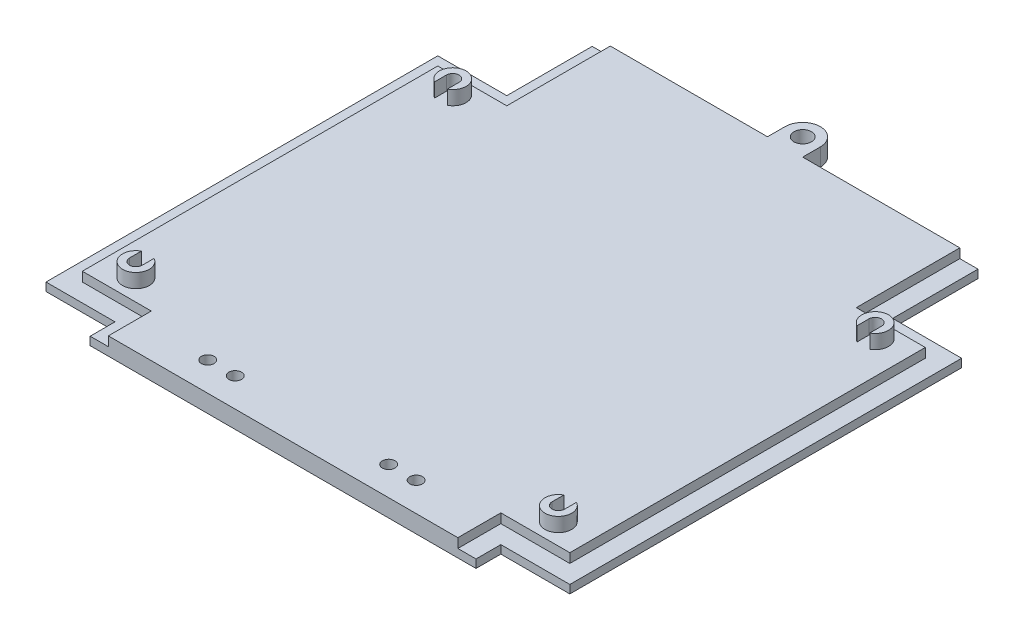
SolidWorks part; units mm, degrees
ref_plane "Front Plane" through (0, 0, 0) normal (0, 0, 1) x (1, 0, 0)
ref_plane "Top Plane" through (0, 0, 0) normal (0, 1, 0) x (1, 0, 0)
ref_plane "Right Plane" through (0, 0, 0) normal (1, 0, 0) x (0, 0, -1)
sketch "Sketch1" plane through (0, 0, 0) normal (0, 1, 0) x (1, 0, 0)
  line L0 (0, 150.2994) -> (0, 181.102)
  line L1 (0, 0) -> (139.192, 0)
  line L2 (0, 0) -> (0, 8.9586)
  line L3 (0, 181.102) -> (139.192, 181.102)
  line L4 (139.192, 0) -> (139.192, 8.9586)
  line L5 (0, 150.2994) -> (-24.892, 150.2994)
  line L7 (0, 8.9586) -> (-24.892, 8.9586)
  line L8 (-24.892, 150.2994) -> (-24.892, 8.9586)
  line L9 (139.192, 8.9586) -> (164.084, 8.9586)
  line L11 (139.192, 150.2994) -> (164.084, 150.2994)
  line L12 (164.084, 8.9586) -> (164.084, 150.2994)
  line L13 (139.192, 150.2994) -> (139.192, 181.102)
  dimension "D1" = 139.192
  dimension "D2" = 181.102
  dimension "D3" = 24.892
  dimension "D4" = 30.8026
  dimension "D5" = 8.9586
extrude "Boss-Extrude1" add sketch "Sketch1" along normal blind 6.35
sketch "Sketch2" plane through (0, 6.35, 0) normal (0, 1, 0) x (1, 0, 0)
  line L0 (69.596, 181.102) -> (69.596, 0) construction
  line L1 (139.192, 181.102) -> (0, 181.102) construction
  line L2 (0, 0) -> (139.192, 0) construction
  line L11 (132.642, 181.102) -> (132.642, 143.7494)
  line L12 (139.192, 181.102) -> (0, 181.102) construction
  line L13 (132.642, 143.7494) -> (157.534, 143.7494)
  line L14 (157.534, 143.7494) -> (157.534, 15.5086)
  line L15 (157.534, 15.5086) -> (132.642, 15.5086)
  line L16 (132.642, 15.5086) -> (132.642, 0)
  line L17 (132.642, 0) -> (139.192, 0)
  line L18 (139.192, 0) -> (139.192, 8.9586)
  line L19 (139.192, 8.9586) -> (164.084, 8.9586)
  line L20 (164.084, 8.9586) -> (164.084, 150.2994)
  line L21 (164.084, 150.2994) -> (139.192, 150.2994)
  line L22 (139.192, 150.2994) -> (139.192, 181.102)
  line L23 (139.192, 181.102) -> (132.642, 181.102)
  line L24 (0, 181.102) -> (6.55, 181.102)
  line L25 (0, 150.2994) -> (0, 181.102)
  line L26 (-24.892, 150.2994) -> (0, 150.2994)
  line L27 (-24.892, 8.9586) -> (-24.892, 150.2994)
  line L28 (0, 8.9586) -> (-24.892, 8.9586)
  line L29 (0, 0) -> (0, 8.9586)
  line L30 (6.55, 0) -> (0, 0)
  line L31 (6.55, 15.5086) -> (6.55, 0)
  line L32 (-18.342, 15.5086) -> (6.55, 15.5086)
  line L33 (-18.342, 143.7494) -> (-18.342, 15.5086)
  line L34 (6.55, 143.7494) -> (-18.342, 143.7494)
  line L35 (6.55, 181.102) -> (6.55, 143.7494)
  dimension "D1" = 6.55
  dimension "D2" = 6.55
  dimension "D3" = 6.55
  dimension "D4" = 6.55
  dimension "D5" = 6.55
extrude "Cut-Extrude1" cut sketch "Sketch2" against normal blind 3.375
sketch "Sketch3" plane through (0, 6.35, 0) normal (0, 1, 0) x (1, 0, 0)
  line L0 (132.642, 181.102) -> (6.55, 181.102) construction
  line L1 (63.246, 181.102) -> (75.946, 181.102)
  line L2 (63.246, 181.102) -> (63.246, 193.802)
  line L3 (63.246, 193.802) -> (75.946, 193.802)
  line L4 (75.946, 181.102) -> (75.946, 193.802)
  line L5 (139.192, 181.102) -> (0, 181.102) construction
  point P6 (69.596, 181.102)
  point P9 (69.596, 181.102)
  dimension "D1" = 12.7
  dimension "D2" = 12.7
extrude "Boss-Extrude2" add sketch "Sketch3" against normal blind 6.35
fillet "Fillet1" radius 6.35 2 edges at (63.246, 3.175, -193.802) (75.946, 3.175, -193.802)
sketch "Sketch4" plane through (0, 6.35, 0) normal (0, 1, 0) x (1, 0, 0)
  circle A0 centre (69.596, 187.452) radius 3.175
  dimension "D1" = 6.35
extrude "Cut-Extrude2" cut sketch "Sketch4" against normal through all
sketch "Sketch5" plane through (0, 0, 0) normal (0, -1, 0) x (1, 0, 0)
  line L0 (107.188, -8.128) -> (107.188, 0) construction
  line L1 (0, 0) -> (139.192, 0) construction
  line L2 (109.474, -10.414) -> (139.192, -10.414) construction
  line L3 (139.192, 0) -> (139.192, -8.9586) construction
  line L4 (104.902, -10.414) -> (99.568, -10.414) construction
  line L5 (39.624, -10.414) -> (34.29, -10.414) construction
  line L7 (94.996, -10.414) -> (44.196, -10.414) construction
  line L8 (29.718, -10.414) -> (0, -10.414) construction
  line L9 (0, -8.9586) -> (0, 0) construction
  circle A0 centre (107.188, -10.414) radius 2.286
  circle A1 centre (97.282, -10.414) radius 2.286
  circle A2 centre (41.91, -10.414) radius 2.286
  circle A3 centre (32.004, -10.414) radius 2.286
  dimension "D2" = 4.572
  dimension "D3" = 4.572
  dimension "D4" = 4.572
  dimension "D5" = 4.572
  dimension "D1" = 8.128
  dimension "D6" = 5.334
  dimension "D7" = 5.334
  dimension "D8" = 50.8
extrude "Cut-Extrude3" cut sketch "Sketch5" against normal blind 12.7
sketch "Sketch6" plane through (0, 6.35, 0) normal (0, 1, 0) x (1, 0, 0)
  line L0 (-32.004, 181.864) -> (-32.004, -21.336) construction
  line L1 (-32.004, -21.336) -> (171.196, -21.336) construction
  line L2 (171.196, -21.336) -> (171.196, 181.864) construction
  line L3 (171.196, 181.864) -> (-32.004, 181.864) construction
  line L4 (6.55, 0) -> (132.642, 0) construction
  line L5 (132.642, 181.102) -> (75.946, 181.102) construction
  line L6 (-4.318, 23.114) -> (-4.318, 27.3642)
  line L7 (-8.89, 137.414) -> (-8.89, 133.1638)
  line L8 (-8.89, 27.3642) -> (-8.89, 23.114)
  line L9 (148.082, 23.114) -> (148.082, 27.3642)
  line L10 (-4.318, 133.1638) -> (-4.318, 137.414)
  line L11 (148.082, 137.414) -> (148.082, 133.1638)
  line L12 (143.51, 27.3642) -> (143.51, 23.114)
  line L14 (143.51, 133.1638) -> (143.51, 137.414)
  arc A0 (-4.318, 137.414) -> (-8.89, 137.414) centre (-6.604, 137.414) ccw
  arc A1 (148.082, 137.414) -> (143.51, 137.414) centre (145.796, 137.414) ccw
  arc A2 (143.51, 23.114) -> (148.082, 23.114) centre (145.796, 23.114) ccw
  arc A3 (-8.89, 23.114) -> (-4.318, 23.114) centre (-6.604, 23.114) ccw
  arc A4 (-4.318, 133.1638) -> (-8.89, 133.1638) centre (-6.604, 137.414) ccw
  arc A5 (148.082, 133.1638) -> (143.51, 133.1638) centre (145.796, 137.414) ccw
  arc A6 (143.51, 27.3642) -> (148.082, 27.3642) centre (145.796, 23.114) ccw
  arc A7 (-8.89, 27.3642) -> (-4.318, 27.3642) centre (-6.604, 23.114) ccw
  circle A8 centre (-6.604, 23.114) radius 4.826 construction
  circle A9 centre (-6.604, 23.114) radius 2.286 construction
  circle A10 centre (-6.604, 137.414) radius 2.286 construction
  circle A11 centre (-6.604, 137.414) radius 4.826 construction
  circle A12 centre (145.796, 23.114) radius 2.286 construction
  circle A13 centre (145.796, 23.114) radius 4.826 construction
  circle A14 centre (145.796, 137.414) radius 2.286 construction
  circle A15 centre (145.796, 137.414) radius 4.826 construction
  point P2 (69.596, -21.336)
  point P7 (69.596, 0)
  dimension "D4" = 4.572
  dimension "D1" = 0.762
  dimension "D2" = 203.2
  dimension "D3" = 203.2
  dimension "D5" = 44.45
  dimension "D6" = 44.45
  dimension "D7" = 25.4
  dimension "D8" = 25.4
  dimension "D9" = 2.54
extrude "Boss-Extrude3" add sketch "Sketch6" along normal blind 5.08
